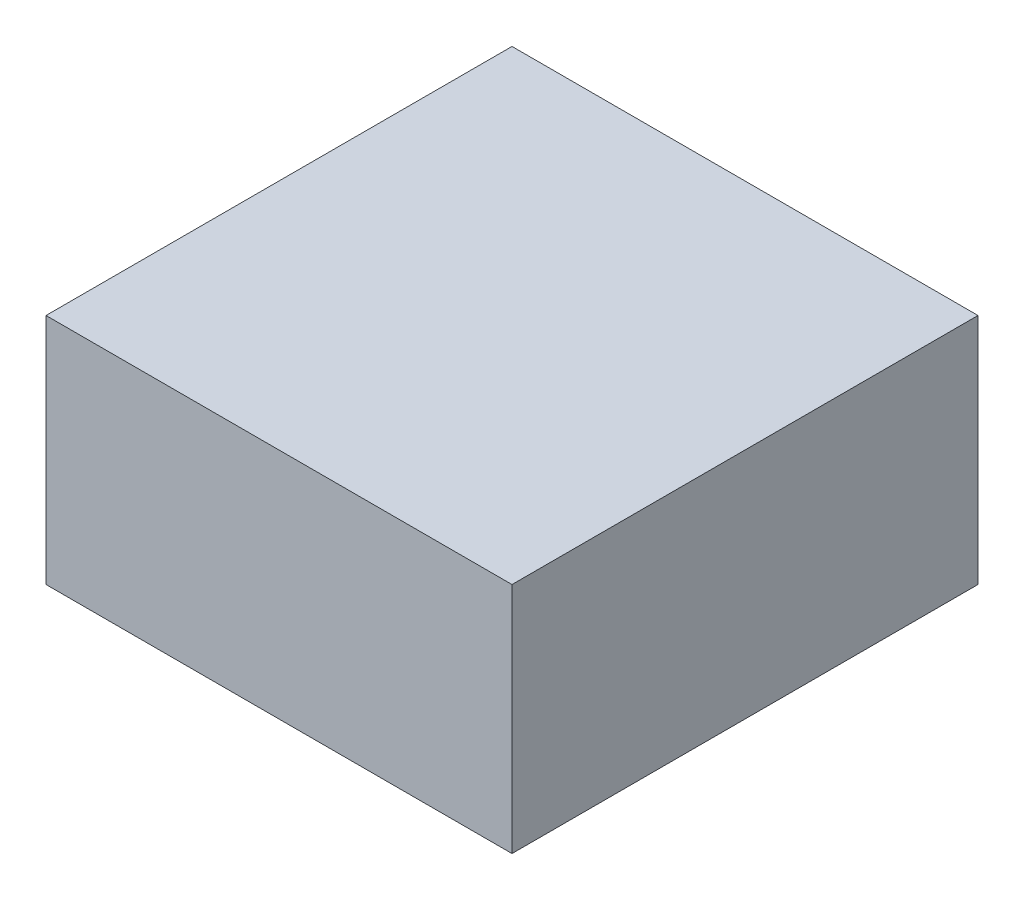
SolidWorks part; units mm, degrees
ref_plane "Front Plane" through (0, 0, 0) normal (0, 0, 1) x (1, 0, 0)
ref_plane "Top Plane" through (0, 0, 0) normal (0, 1, 0) x (1, 0, 0)
ref_plane "Right Plane" through (0, 0, 0) normal (1, 0, 0) x (0, 0, -1)
sketch "Case Sketch" plane through (0, 0, 0) normal (1, 0, 0) x (0, 0, -1)
  line L0 (6.35, 92.65) -> (6.35, 99)
  line L1 (6.35, 99) -> (-6.35, 99)
  line L2 (-6.35, 99) -> (-6.35, 92.65)
  line L3 (-6.35, 92.65) -> (6.35, 92.65)
extrude "Case" add sketch "Case Sketch" along normal mid plane 12.7
ref_axis "Engine Axis" through (6.985, 0, 0) along (-1, 0, 0)
